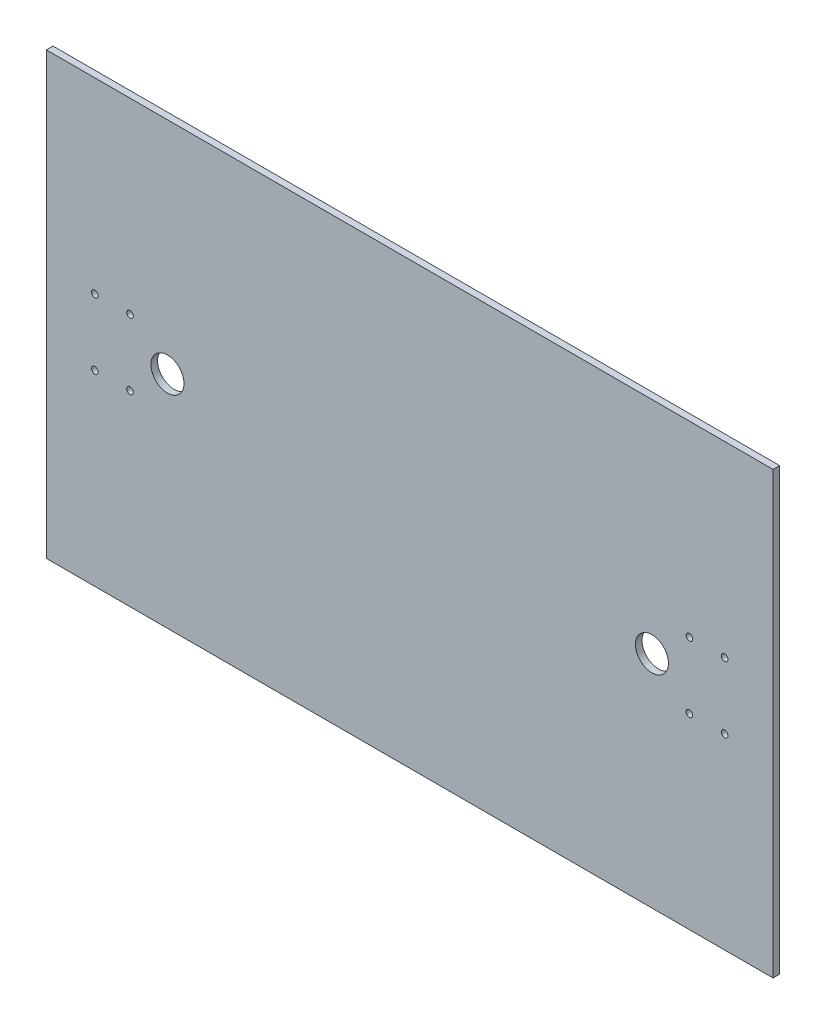
SolidWorks part; units mm, degrees
ref_plane "Alzado" through (0, 0, 0) normal (0, 0, 1) x (1, 0, 0)
ref_plane "Planta" through (0, 0, 0) normal (0, 1, 0) x (1, 0, 0)
ref_plane "Vista lateral" through (0, 0, 0) normal (1, 0, 0) x (0, 0, -1)
sketch "Croquis1" plane through (0, 0, 0) normal (0, 0, 1) x (1, 0, 0)
  line L1 (-165, 100) -> (165, 100)
  line L2 (-165, 100) -> (-165, -100)
  line L3 (-165, -100) -> (165, -100)
  line L4 (165, 100) -> (165, -100)
  line L5 (-165, 100) -> (165, -100) construction
  line L6 (-165, -100) -> (165, 100) construction
  point P0 (0, 0)
  dimension "D1" = 330
  dimension "D2" = 200
extrude "Saliente-Extruir1" add sketch "Croquis1" along normal blind 3
sketch "Croquis2" plane through (0, 0, 3) normal (0, 0, 1) x (1, 0, 0)
  line L0 (-165, 0) -> (165, 0) construction
  line L1 (-165, 100) -> (-165, -100) construction
  line L2 (165, -100) -> (165, 100) construction
  line L3 (0, 100) -> (0, -100) construction
  line L4 (165, 100) -> (-165, 100) construction
  line L5 (-165, -100) -> (165, -100) construction
  circle A0 centre (-110, 0) radius 7.5
  circle A1 centre (110, 0) radius 7.5
  circle A2 centre (-143, 15) radius 1.5
  circle A6 centre (-127, 15) radius 1.5
  circle A7 centre (-127, -15) radius 1.5
  circle A8 centre (-143, -15) radius 1.5
  circle A9 centre (127, 15) radius 1.5
  circle A10 centre (127, -15) radius 1.5
  circle A11 centre (143, -15) radius 1.5
  circle A12 centre (143, 15) radius 1.5
  dimension "D1" = 15
  dimension "D3" = 3
  dimension "D5" = 15
  dimension "D6" = 3
  dimension "D7" = 16
  dimension "D2" = 55
  dimension "D4" = 22
extrude "Cortar-Extruir1" cut sketch "Croquis2" against normal through all
equation "\"largo\"= 330mm"
equation "\"ancho\"= 200mm"
